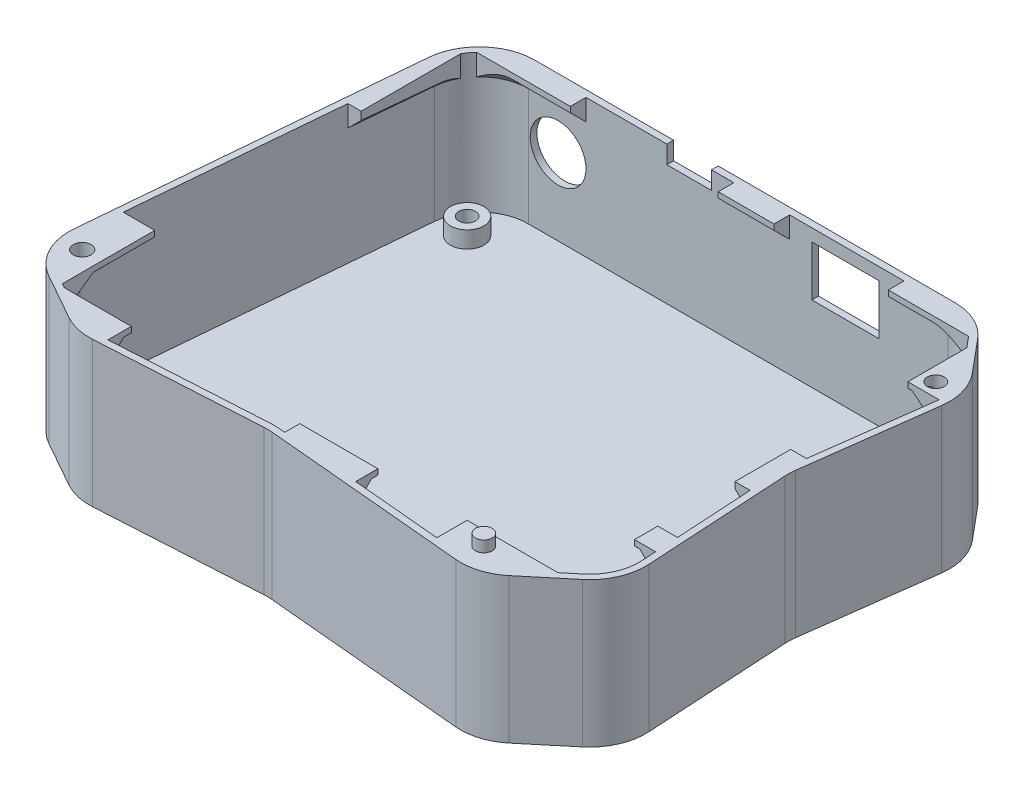
SolidWorks part; units mm, degrees
ref_plane "Front Plane" through (0, 0, 0) normal (0, 0, 1) x (1, 0, 0)
ref_plane "Top Plane" through (0, 0, 0) normal (0, 1, 0) x (1, 0, 0)
ref_plane "Right Plane" through (0, 0, 0) normal (1, 0, 0) x (0, 0, -1)
sketch "Sketch1" plane through (0, 0, 0) normal (0, 1, 0) x (1, 0, 0)
  line L1 (-50, -40) -> (50, -40)
  line L2 (-50, -40) -> (-50, 40)
  line L3 (-50, 40) -> (50, 40)
  line L4 (50, -40) -> (50, 40)
  line L5 (-50, -40) -> (50, 40) construction
  line L6 (-50, 40) -> (50, -40) construction
  point P0 (0, 0)
  dimension "D1" = 100
  dimension "D2" = 80
extrude "Boss-Extrude1" [suppressed] add sketch "Sketch1" along normal blind 30
shell "Shell1" [suppressed] thickness 1.6
sketch "Sketch2" plane through (0, 0, 0) normal (0, 1, 0) x (1, 0, 0)
  line L1 (2, -76) -> (92, -76) construction
  line L2 (2, -76) -> (2, -6) construction
  line L3 (2, -6) -> (92, -6) construction
  line L4 (92, -76) -> (92, -6) construction
  line L5 (2, -76) -> (92, -6) construction
  line L6 (2, -6) -> (92, -76) construction
  point P0 (47, -41)
  dimension "D1" = 90
  dimension "D2" = 70
  dimension "D3" = 47
  dimension "D4" = 41
sketch "Sketch3" plane through (0, 0, 0) normal (0, 1, 0) x (1, 0, 0)
  line L0 (0, 0) -> (89.1154, 0)
  line L1 (89.1154, 0) -> (99.7879, -12.807)
  line L2 (99.7879, -12.807) -> (96.0525, -41.2225)
  line L3 (96.0525, -41.2225) -> (97.9202, -73.1066)
  line L4 (97.9202, -73.1066) -> (83.6829, -84.971)
  line L5 (83.6829, -84.971) -> (42.5817, -81.2346)
  line L6 (42.5817, -81.2346) -> (9.8977, -83.1491)
  line L7 (9.8977, -83.1491) -> (-6.5369, -73.9071)
  line L8 (-6.5369, -73.9071) -> (0, 0)
  dimension "D1" = 9.8977
  dimension "D2" = 42.5817
  dimension "D3" = 83.6829
  dimension "D4" = 89.1154
  dimension "D5" = 96.0525
  dimension "D6" = 97.9202
  dimension "D7" = 99.7879
  dimension "D8" = 6.5369
  dimension "D9" = 12.807
  dimension "D10" = 41.2225
  dimension "D11" = 73.1066
  dimension "D12" = 73.9071
  dimension "D13" = 81.2346
extrude "Boss-Extrude2" add sketch "Sketch3" along normal blind 26
fillet "Fillet1" radius 10 9 edges at (0, 13, 0) (89.1154, 13, 0) (96.0525, 13, 41.2225) (99.7879, 13, 12.807) (83.6829, 13, 84.971) (97.9202, 13, 73.1066) (42.5817, 13, 81.2346) (9.8977, 13, 83.1491) (-6.5369, 13, 73.9071)
shell "Shell2" thickness 1.2 removed face at (57.1677, 26, 50.2298)
sketch "Sketch5" plane through (0, 1.2, 0) normal (0, 1, 0) x (1, 0, 0)
  circle A0 centre (5.5, -8.5) radius 3
  circle A1 centre (88.5, -8.5) radius 3
  circle A2 centre (88.5, -73.5) radius 3
  circle A3 centre (5.5, -73.5) radius 3
  dimension "D1" = 6
  dimension "D2" = 32.5
  dimension "D3" = 3.5
  dimension "D6" = 32.5
  dimension "D7" = 3.5
  dimension "D4" = 2
  dimension "D5" = 2
extrude "Boss-Extrude3" add sketch "Sketch5" along normal blind 3
sketch "Sketch6" plane through (0, 4.2, 0) normal (0, 1, 0) x (1, 0, 0)
  circle A0 centre (5.5, -73.5) radius 1.35
  circle A1 centre (88.5, -8.5) radius 1.35
  circle A2 centre (5.5, -73.5) radius 3 construction
  circle A4 centre (88.5, -8.5) radius 3 construction
  dimension "D1" = 2.7
extrude "Boss-Extrude4" add sketch "Sketch6" along normal blind 2
sketch "Sketch7" plane through (0, 4.2, 0) normal (0, 1, 0) x (1, 0, 0)
  circle A0 centre (5.5, -8.5) radius 1.5
  circle A1 centre (88.5, -73.5) radius 1.5
  dimension "D1" = 3
extrude "Cut-Extrude2" cut sketch "Sketch7" against normal through all
ref_plane "Plane1" through (0, 5.8, 0) normal (0, 1, 0) x (1, 0, 0)
ref_point "Point1"
ref_point "Point2"
sketch "Sketch8" plane through (0, 0, 0) normal (0, 0, -1) x (-1, 0, 0)
  line L0 (14.8186, 5.8) -> (-14.8186, 5.8) construction
  line L2 (-72, 14.8) -> (-60, 14.8)
  line L3 (-42, 22.8) -> (-34, 22.8)
  line L4 (-42, 22.8) -> (-42, 28.8)
  line L5 (-42, 28.8) -> (-34, 28.8)
  line L6 (-34, 22.8) -> (-34, 28.8)
  line L7 (-42, 22.8) -> (-34, 28.8) construction
  line L8 (-42, 28.8) -> (-34, 22.8) construction
  line L9 (-72, 14.8) -> (-72, 23.8)
  line L10 (-72, 23.8) -> (-60, 23.8)
  line L11 (-60, 14.8) -> (-60, 23.8)
  line L12 (-72, 14.8) -> (-60, 23.8) construction
  line L13 (-72, 23.8) -> (-60, 14.8) construction
  circle A0 centre (-14.5, 14.9) radius 5
  point P3 (-38, 25.8)
  point P5 (-66, 19.3)
  point P8 (-5.5, 5.8)
  dimension "D3" = 10
  dimension "D1" = 9.1
  dimension "D2" = 9
  dimension "D4" = 23
  dimension "D5" = 6
  dimension "D6" = 8
  dimension "D7" = 32.5
  dimension "D8" = 12
  dimension "D9" = 9
  dimension "D10" = 60.5
  dimension "D11" = 9
extrude "Cut-Extrude3" cut sketch "Sketch8" against normal up to next
sketch "Sketch9" plane through (0, 26, 0) normal (0, 1, 0) x (1, 0, 0)
  line L0 (34, -1.2) -> (9.1546, -1.2) construction
  line L1 (19.5, -1.2) -> (2.7172, -1.2)
  line L2 (19.5, -1.2) -> (19.5, -4)
  line L3 (19.5, -4) -> (2.7172, -4)
  line L4 (2.7172, -1.2) -> (2.7172, -4)
  line L5 (84.4316, -1.2) -> (42, -1.2) construction
  line L6 (46, -1.2) -> (56, -1.2)
  line L7 (46, -1.2) -> (46, -4)
  line L8 (46, -4) -> (56, -4)
  line L9 (56, -1.2) -> (56, -4)
  line L10 (34, 0) -> (9.1546, 0) construction
  line L11 (76.5, -1.2) -> (90.869, -1.2)
  line L12 (76.5, -1.2) -> (76.5, -4)
  line L13 (76.5, -4) -> (90.869, -4)
  line L14 (90.869, -1.2) -> (90.869, -4)
  line L15 (92.5, -61.3168) -> (100.5, -61.3168)
  line L16 (92.5, -61.3168) -> (92.5, -65.5)
  line L17 (92.5, -5.936) -> (100.5, -5.936)
  line L18 (100.5, -61.3168) -> (100.5, -65.5)
  line L19 (2.3004, -77.5) -> (14.3004, -77.5)
  line L20 (2.3004, -77.5) -> (2.3004, -85.5)
  line L21 (2.3004, -85.5) -> (14.3004, -85.5)
  line L22 (90.7737, -77.5) -> (90.7737, -85.5)
  line L23 (1.5, -77.0499) -> (-6.5, -77.0499)
  line L24 (1.5, -77.0499) -> (1.5, -60.5)
  line L25 (1.5, -5.6586) -> (-6.5, -5.6586)
  line L26 (-6.5, -77.0499) -> (-6.5, -60.5)
  line L27 (42, 0) -> (42, -1.2) construction
  line L28 (96.0628, -10.2114) -> (91.192, -4.3664) construction
  line L29 (92.5, -16.5) -> (100.5, -16.5)
  line L30 (92.5, -37.5) -> (100.5, -37.5)
  line L31 (92.5, -47.5) -> (100.5, -47.5)
  line L32 (92.5, -65.5) -> (100.5, -65.5)
  line L33 (92.5, -47.5) -> (92.5, -37.5)
  line L34 (100.5, -47.5) -> (100.5, -37.5)
  line L35 (100.5, -16.5) -> (100.5, -5.936)
  line L36 (92.5, -16.5) -> (92.5, -5.936)
  line L37 (74.5, -77.5) -> (74.5, -85.5)
  line L38 (58.5, -77.5) -> (58.5, -85.5)
  line L39 (58.5, -85.5) -> (44.5, -85.5)
  line L40 (44.5, -85.5) -> (44.5, -77.5)
  line L41 (14.3004, -77.5) -> (14.3004, -85.5)
  line L42 (44.5, -77.5) -> (58.5, -77.5)
  line L43 (44.5, -85.5) -> (58.5, -85.5)
  line L44 (74.5, -77.5) -> (90.7737, -77.5)
  line L45 (74.5, -85.5) -> (90.7737, -85.5)
  line L46 (86.0967, -81.3974) -> (93.2759, -75.4148) construction
  line L47 (-0.3203, -76.0262) -> (7.9285, -80.665) construction
  line L48 (-6.5, -60.5) -> (1.5, -60.5)
  line L49 (-6.5, -23.5) -> (1.5, -23.5)
  line L50 (-6.5, -23.5) -> (-6.5, -5.6586)
  line L51 (1.5, -23.5) -> (1.5, -5.6586)
  arc A0 (9.1546, -1.2) -> (0.3888, -9.2247) centre (9.1546, -10) ccw construction
  arc A1 (93.2759, -75.4148) -> (96.4272, -68.1399) centre (87.6422, -68.6545) ccw construction
  circle A2 centre (5.5, -8.5) radius 1.5 construction
  arc A3 (91.192, -4.3664) -> (84.4316, -1.2) centre (84.4316, -10) ccw construction
  circle A4 centre (88.5, -73.5) radius 1.5 construction
  circle A5 centre (88.5, -8.5) radius 1.35 construction
  circle A8 centre (5.5, -73.5) radius 1.35 construction
  circle A9 centre (5.5, -73.5) radius 1.35 construction
  point P73 (-0.3203, -76.0262)
  point P75 (0.2973, -76.3735)
  point P80 (1.5, -5.6586)
  line M5 (42, -1.2) -> (84.4316, -1.2)
  arc M6 (84.4316, -1.2) -> (91.192, -4.3664) centre (84.4316, -10) cw
  line M7 (91.192, -4.3664) -> (96.0628, -10.2114)
  arc M8 (96.0628, -10.2114) -> (98.0274, -16.992) centre (89.3025, -15.845) cw
  line M9 (98.0274, -16.992) -> (94.9864, -40.1253)
  arc M10 (94.9864, -40.1253) -> (94.91, -42.24) centre (106.0909, -41.585) ccw
  line M11 (94.91, -42.24) -> (96.4272, -68.1399)
  line M13 (93.2759, -75.4148) -> (86.0967, -81.3974)
  arc M14 (86.0967, -81.3974) -> (79.6664, -83.4009) centre (80.4631, -74.6371) cw
  line M15 (79.6664, -83.4009) -> (43.4346, -80.1071)
  arc M16 (43.4346, -80.1071) -> (41.7656, -80.0803) centre (42.4206, -91.2611) ccw
  line M17 (41.7656, -80.0803) -> (12.7565, -81.7796)
  arc M18 (12.7565, -81.7796) -> (7.9285, -80.665) centre (12.2419, -72.9946) cw
  line M19 (7.9285, -80.665) -> (-0.3203, -76.0262)
  arc M20 (-0.3203, -76.0262) -> (-4.7727, -67.5806) centre (3.9931, -68.3559) cw
  line M21 (-4.7727, -67.5806) -> (0.3888, -9.2247)
  arc M22 (0.3888, -9.2247) -> (9.1546, -1.2) centre (9.1546, -10) cw
  line M23 (9.1546, -1.2) -> (34, -1.2)
  dimension "D2" = 14
  dimension "D5" = 4
  dimension "D7" = 8
  dimension "D8" = 26
  dimension "D10" = 8
  dimension "D11" = 14
  dimension "D13" = 8
  dimension "D16" = 12
  dimension "D1" = 4
  dimension "D3" = 4
  dimension "D4" = 10
  dimension "D6" = 8
  dimension "D9" = 10
  dimension "D12" = 4
  dimension "D14" = 30
  dimension "D15" = 14
  dimension "D17" = 4
  dimension "D18" = 8
  dimension "D19" = 13
  dimension "D20" = 15
  dimension "D21" = 12
extrude "Boss-Extrude5" add sketch "Sketch9" against normal blind 1 contours L22 L19 L20 M19 M18 M17 M16 M15 M14 M13 | L24 L25 M21 M20 M19 | L3 L2 M23 M22 | L36 L29 M8 M7 | L33 L31 L30 M11 M10 M9 | L16 L32 L15 M11 | L9 L7 L8 M5 | L12 L13 M6 M5 | L44 L37 M15 M14 M13 | L42 L40 L38 M15 | L49 L51 M22 M21 region at (12.0271, 26, 2.6792) region at (81.0736, 26, 80.0876) region at (51.9445, 26, 79.1904) region at (9.901, 26, 79.2775) region at (-1.3233, 26, 67.8138) region at (0.6347, 26, 16.3795) region at (94.3257, 26, 63.4318) region at (93.7814, 26, 42.4993) region at (94.7832, 26, 12.6318) region at (82.7806, 26, 2.6946) region at (51, 26, 2.6)
chamfer "Chamfer1" distance 2.8 angle 45 15 edges at (95.159, 25, 38.8127) (94.8982, 25, 41.1808) (95.0641, 25, 44.87) (5.6446, 25, 1.9303) (14.3273, 25, 1.2) (87.9416, 25, 1.9303) (80.4658, 25, 1.2) (51, 25, 1.2) (0.753, 25, 7.382) (-0.2425, 25, 16.3623) (13.5284, 25, 81.7344) (5.1144, 25, 79.0825) (10.2624, 25, 81.5691) (51.5, 25, 80.8404) (96.15, 25, 63.4084)
chamfer "Chamfer2" distance 4 angle 50 8 edges at (94.2814, 25, 8.0737) (97.6827, 25, 13.1595) (88.4352, 25, 79.4487) (77.0832, 25, 83.1661) (83.0808, 25, 83.0387) (0.5898, 25, 76.5381) (-4.4595, 25, 64.0403) (-3.7914, 25, 72.4597) first distance on face at (93.2516, 17.4, 6.8379) first distance on face at (97.6103, 17.4, 14.5009) first distance on face at (90.0488, 17.4, 78.1041) first distance on face at (60.1202, 20.08, 81.624) first distance on face at (82.9812, 13.1, 82.719) first distance on face at (2.8521, 18.6, 77.8103) first distance on face at (-2.351, 18.6, 40.2013) first distance on face at (-3.1689, 13.1, 72.1316)
sketch "Sketch11" plane through (0, 26, 0) normal (0, 1, 0) x (1, 0, 0)
  circle A0 centre (95, -14) radius 1.5
  circle A2 centre (-2, -70) radius 1.6
  dimension "D1" = 3
  dimension "D2" = 95
  dimension "D3" = 14
  dimension "D4" = 70
  dimension "D5" = 2
extrude "Cut-Extrude4" cut sketch "Sketch11" against normal blind 10
sketch "Sketch12" plane through (0, 26, 0) normal (0, 1, 0) x (1, 0, 0)
  circle A0 centre (80, -80) radius 1.5
  dimension "D3" = 3
  dimension "D1" = 80
  dimension "D2" = 80
extrude "Boss-Extrude6" add sketch "Sketch12" along normal blind 2
